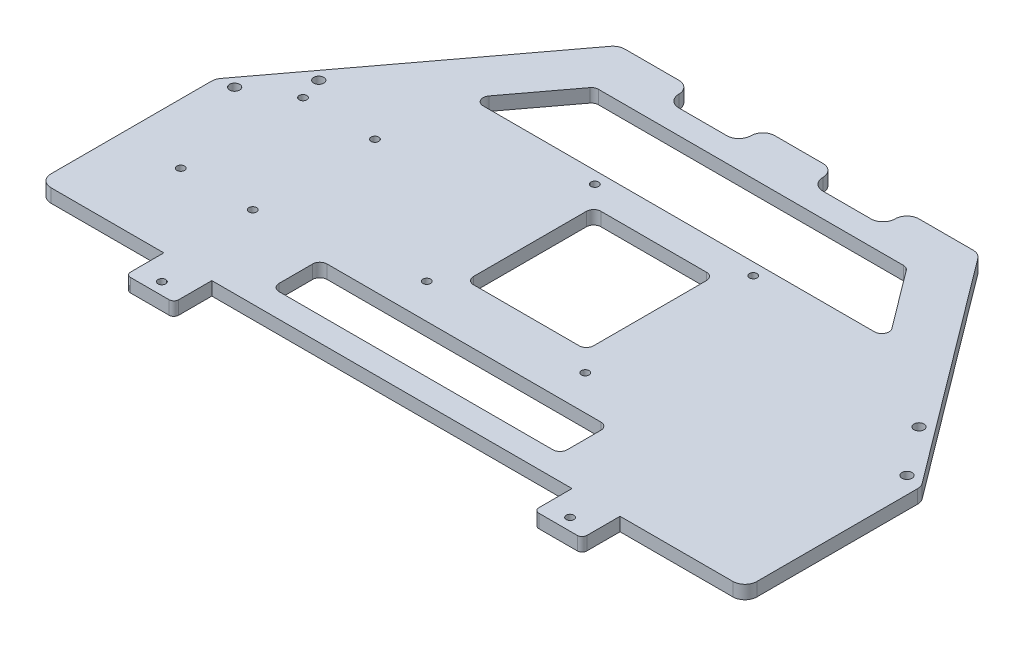
SolidWorks part; units mm, degrees
material "t5ハニカムプラダン"
ref_plane "正面" through (0, 0, 0) normal (0, 0, 1) x (1, 0, 0)
ref_plane "平面" through (0, 0, 0) normal (0, 1, 0) x (1, 0, 0)
ref_plane "右側面" through (0, 0, 0) normal (1, 0, 0) x (0, 0, -1)
sketch "ｽｹｯﾁ1" plane through (0, 0, 0) normal (0, 1, 0) x (1, 0, 0)
  line L0 (0, 0) -> (0, 132.75) construction
  line L1 (-147, 36.75) -> (147, 36.75)
  line L2 (-147, 36.75) -> (-147, -36.75)
  line L3 (-147, -36.75) -> (147, -36.75)
  line L4 (147, 36.75) -> (147, -36.75)
  line L5 (-147, 36.75) -> (147, -36.75) construction
  line L6 (-147, -36.75) -> (147, 36.75) construction
  line L7 (75, 132.75) -> (-75, 132.75)
  line L8 (-75, 132.75) -> (-147, 36.75)
  line L9 (75, 132.75) -> (147, 36.75)
  line L10 (140, 37.75) -> (125, 57.75) construction
  circle A0 centre (140, 37.75) radius 2.1
  circle A1 centre (-140, 37.75) radius 2.1
  circle A2 centre (125, 57.75) radius 2.1
  circle A3 centre (-125, 57.75) radius 2.1
  point P0 (0, 0)
  dimension "D5" = 4.2
  dimension "D1" = 294
  dimension "D2" = 73.5
  dimension "D3" = 169.5
  dimension "D4" = 150
  dimension "D6" = 280
  dimension "D7" = 74.5
  dimension "D8" = 25
extrude "ﾎﾞｽ - 押し出し1" add sketch "ｽｹｯﾁ1" along normal blind 5.6 contours L9 L7 L8 L1 | L4 L1 L2 L3 A0 A1 region at (0, 0, -79.632) region at (0, 0, 0.0097)
sketch "ｽｹｯﾁ2" plane through (0, 0, 0) normal (0, 1, 0) x (1, 0, 0)
  line L0 (-147, -36.75) -> (147, -36.75) construction
  line L1 (-95, -36.75) -> (-75, -36.75)
  line L2 (-95, -36.75) -> (-95, -52.55)
  line L3 (-95, -52.55) -> (-75, -52.55)
  line L4 (-75, -36.75) -> (-75, -52.55)
  line L5 (0, -36.75) -> (0, 132.75) construction
  line L6 (75, 132.75) -> (-75, 132.75) construction
  line L7 (-85, -52.55) -> (-85, -47.55) construction
  line L8 (85, -52.55) -> (85, -47.55) construction
  line L9 (75, -36.75) -> (75, -52.55)
  line L10 (95, -52.55) -> (75, -52.55)
  line L11 (95, -36.75) -> (95, -52.55)
  line L12 (95, -36.75) -> (75, -36.75)
  circle A0 centre (-85, -47.55) radius 1.6
  circle A1 centre (85, -47.55) radius 1.6
  dimension "D3" = 3.2
  dimension "D1" = 15.8
  dimension "D2" = 20
  dimension "D4" = 5
  dimension "D5" = 150
extrude "ﾎﾞｽ - 押し出し2" add sketch "ｽｹｯﾁ2" along normal blind 5.6
sketch "ｽｹｯﾁ3" plane through (0, 5.6, 0) normal (0, 1, 0) x (1, 0, 0)
  line L0 (75, 132.75) -> (-75, 132.75) construction
  line L1 (-30, 77.75) -> (36, 77.75) construction
  line L2 (-30, 77.75) -> (-30, 7.75) construction
  line L3 (-30, 7.75) -> (36, 7.75) construction
  line L4 (36, 77.75) -> (36, 7.75) construction
  line L5 (-30, 77.75) -> (36, 7.75) construction
  line L6 (-30, 7.75) -> (36, 77.75) construction
  line L7 (-147, 36.75) -> (-147, -36.75) construction
  line L8 (3, 77.75) -> (3, 42.75) construction
  line L9 (3, 42.75) -> (36, 42.75) construction
  line L10 (147, 36.75) -> (147, -36.75) construction
  line L11 (22.75, 66.5) -> (51.25, 66.5) construction
  line L12 (22.75, 66.5) -> (22.75, 19) construction
  line L13 (22.75, 19) -> (51.25, 19) construction
  line L14 (51.25, 66.5) -> (51.25, 19) construction
  line L15 (22.75, 66.5) -> (51.25, 19) construction
  line L16 (22.75, 19) -> (51.25, 66.5) construction
  line L17 (37, 66.5) -> (37, 42.75) construction
  line L18 (37, 42.75) -> (51.25, 42.75) construction
  line L19 (22.75, 19) -> (51.25, 19) construction
  line L20 (-107, 48.19) -> (-107, 22.75) construction
  line L21 (-121.995, 48.19) -> (-92.005, 48.19) construction
  line L22 (-121.995, 48.19) -> (-121.995, -2.69) construction
  line L23 (-121.995, -2.69) -> (-92.005, -2.69) construction
  line L24 (-92.005, 48.19) -> (-92.005, -2.69) construction
  line L25 (-121.995, 48.19) -> (-92.005, -2.69) construction
  line L26 (-121.995, -2.69) -> (-92.005, 48.19) construction
  line L27 (-107, 22.75) -> (-92.005, 22.75) construction
  circle A0 centre (36, 77.75) radius 1.6
  circle A1 centre (-30, 77.75) radius 1.6
  circle A2 centre (-30, 7.75) radius 1.6
  circle A3 centre (36, 7.75) radius 1.6
  circle A4 centre (51.25, 66.5) radius 2.1 construction
  circle A5 centre (37, 66.5) radius 2.1 construction
  circle A6 centre (22.75, 66.5) radius 2.1 construction
  circle A7 centre (22.75, 19) radius 2.1 construction
  circle A8 centre (37, 19) radius 2.1 construction
  circle A9 centre (51.25, 19) radius 2.1 construction
  circle A10 centre (-92.005, 48.19) radius 1.6
  circle A11 centre (-92.005, -2.69) radius 1.6
  circle A12 centre (-121.995, -2.69) radius 1.6
  circle A13 centre (-121.995, 48.19) radius 1.6
  point P0 (3, 42.75)
  point P16 (37, 42.75)
  point P33 (-107, 22.75)
  dimension "D5" = 3.2
  dimension "D10" = 4.2
  dimension "D1" = 66
  dimension "D2" = 70
  dimension "D3" = 90
  dimension "D4" = 150
  dimension "D6" = 28.5
  dimension "D7" = 47.5
  dimension "D8" = 90
  dimension "D9" = 110
  dimension "D11" = 29.99
  dimension "D12" = 50.88
  dimension "D13" = 110
  dimension "D14" = 40
extrude "ｶｯﾄ - 押し出し1" cut sketch "ｽｹｯﾁ3" against normal through all
sketch "ｽｹｯﾁ4" plane through (0, 5.6, 0) normal (0, 1, 0) x (1, 0, 0)
  line L0 (36, 7.75) -> (-30, 77.75) construction
  line L1 (131, 24.75) -> (65, 112.75)
  line L2 (-22, 69.2652) -> (28, 69.2652)
  line L3 (-22, 69.2652) -> (-22, 16.2348)
  line L4 (-22, 16.2348) -> (28, 16.2348)
  line L5 (28, 69.2652) -> (28, 61.5)
  line L6 (-22, 69.2652) -> (28, 16.2348) construction
  line L7 (-22, 16.2348) -> (28, 69.2652) construction
  line L8 (65, 112.75) -> (-65, 112.75)
  line L9 (-65, 112.75) -> (-131, 24.75)
  line L10 (-87.5, 82.75) -> (87.5, 82.75)
  line L11 (0, 0) -> (0, -16.75) construction
  line L12 (28, 61.5) -> (28, 24)
  line L13 (-60, -26.75) -> (60, -26.75)
  line L14 (-60, -26.75) -> (-60, -6.75)
  line L15 (-60, -6.75) -> (60, -6.75)
  line L16 (60, -26.75) -> (60, -6.75)
  line L17 (-60, -26.75) -> (60, -6.75) construction
  line L18 (-60, -6.75) -> (60, -26.75) construction
  line L20 (28, 61.5) -> (28, 24) construction
  line L21 (-75, 132.75) -> (-147, 36.75)
  line L22 (-147, 36.75) -> (-147, -36.75)
  line L23 (-147, -36.75) -> (-95, -36.75)
  line L24 (-95, -36.75) -> (-95, -52.55)
  line L25 (-95, -52.55) -> (-75, -52.55)
  line L26 (-75, -52.55) -> (-75, -36.75)
  line L27 (-75, -36.75) -> (75, -36.75)
  line L28 (75, -36.75) -> (75, -52.55)
  line L29 (75, -52.55) -> (95, -52.55)
  line L30 (95, -52.55) -> (95, -36.75)
  line L31 (95, -36.75) -> (147, -36.75)
  line L32 (147, -36.75) -> (147, 36.75)
  line L33 (147, 36.75) -> (75, 132.75)
  line L34 (75, 132.75) -> (-75, 132.75)
  line L35 (-75, 132.75) -> (-147, 36.75)
  line L36 (-147, 36.75) -> (-147, -36.75)
  line L37 (-147, -36.75) -> (-95, -36.75)
  line L38 (-95, -36.75) -> (-95, -52.55)
  line L39 (-95, -52.55) -> (-75, -52.55)
  line L40 (-75, -52.55) -> (-75, -36.75)
  line L41 (-75, -36.75) -> (75, -36.75)
  line L42 (75, -36.75) -> (75, -52.55)
  line L43 (75, -52.55) -> (95, -52.55)
  line L44 (95, -52.55) -> (95, -36.75)
  line L45 (95, -36.75) -> (147, -36.75)
  line L46 (147, -36.75) -> (147, 36.75)
  line L47 (147, 36.75) -> (75, 132.75)
  line L48 (75, 132.75) -> (-75, 132.75)
  line L53 (28, 24) -> (28, 16.2348)
  circle A1 centre (85, -47.55) radius 1.6
  circle A2 centre (85, -47.55) radius 1.6
  circle A3 centre (36, 77.75) radius 1.6
  circle A4 centre (36, 77.75) radius 1.6
  circle A5 centre (-140, 37.75) radius 2.1
  circle A6 centre (-140, 37.75) radius 2.1
  circle A7 centre (140, 37.75) radius 2.1
  circle A8 centre (140, 37.75) radius 2.1
  circle A11 centre (36, 7.75) radius 1.6
  circle A12 centre (36, 7.75) radius 1.6
  circle A13 centre (-30, 7.75) radius 1.6
  circle A14 centre (-30, 7.75) radius 1.6
  circle A15 centre (-30, 77.75) radius 1.6
  circle A16 centre (-30, 77.75) radius 1.6
  circle A17 centre (-121.995, 48.19) radius 1.6
  circle A18 centre (-121.995, 48.19) radius 1.6
  circle A19 centre (-121.995, -2.69) radius 1.6
  circle A20 centre (-121.995, -2.69) radius 1.6
  circle A21 centre (-92.005, -2.69) radius 1.6
  circle A22 centre (-92.005, -2.69) radius 1.6
  circle A23 centre (-92.005, 48.19) radius 1.6
  circle A24 centre (-92.005, 48.19) radius 1.6
  circle A35 centre (-85, -47.55) radius 1.6
  circle A36 centre (-85, -47.55) radius 1.6
  point P0 (3, 42.75)
  point P85 (39.625, 42.75)
  dimension "D19" = 50
  dimension "D22" = 30
  dimension "D23" = 10
  dimension "D24" = 20
  dimension "D25" = 120
  dimension "D1" = 0
  dimension "D2" = 0
  dimension "D3" = 0
  dimension "D4" = 0
  dimension "D6" = 0
  dimension "D7" = 0
  dimension "D8" = 0
  dimension "D9" = 0
  dimension "D10" = 0
  dimension "D11" = 0
  dimension "D12" = 0
  dimension "D18" = 0
  dimension "D20" = 0
  dimension "D21" = 20
extrude "ｶｯﾄ - 押し出し2" cut sketch "ｽｹｯﾁ4" against normal through all contours L9 L10 L1 L8 | L5 L2 L3 L4 | L13 L16 L15 L14 region at (0, 5.6, -97.0123) region at (3, 5.6, -42.75) region at (0, 5.6, 16.75)
sketch "ｽｹｯﾁ6" plane through (0, 5.6, 0) normal (0, 1, 0) x (1, 0, 0)
  line L0 (0, 132.75) -> (0, 127.75) construction
  line L1 (75, 132.75) -> (-75, 132.75) construction
  line L3 (-45, 122.75) -> (45, 122.75)
  line L4 (-45, 122.75) -> (-45, 132.75)
  line L5 (-45, 132.75) -> (45, 132.75)
  line L6 (45, 122.75) -> (45, 132.75)
  line L7 (-45, 122.75) -> (45, 132.75) construction
  line L8 (-45, 132.75) -> (45, 122.75) construction
  dimension "D1" = 90
  dimension "D2" = 10
extrude "ｶｯﾄ - 押し出し3" cut sketch "ｽｹｯﾁ6" against normal through all
sketch "ｽｹｯﾁ7" plane through (0, 5.6, 0) normal (0, 1, 0) x (1, 0, 0)
  line L0 (0, 122.75) -> (0, 127.75) construction
  line L1 (-45, 122.75) -> (45, 122.75) construction
  line L2 (75, 132.75) -> (45, 132.75) construction
  line L3 (-15, 132.75) -> (15, 132.75)
  line L4 (-15, 132.75) -> (-15, 122.75)
  line L5 (-15, 122.75) -> (15, 122.75)
  line L6 (15, 132.75) -> (15, 122.75)
  line L7 (-15, 132.75) -> (15, 122.75) construction
  line L8 (-15, 122.75) -> (15, 132.75) construction
  line L9 (45, 122.75) -> (45, 132.75) construction
  dimension "D1" = 30
extrude "ﾎﾞｽ - 押し出し3" add sketch "ｽｹｯﾁ7" against normal blind 5.6
fillet "ﾌｨﾚｯﾄ1" radius 3 12 edges at (-22, 2.8, -16.2348) (28, 2.8, -16.2348) (87.5, 2.8, -82.75) (28, 2.8, -69.2652) (65, 2.8, -112.75) (-22, 2.8, -69.2652) (-65, 2.8, -112.75) (-87.5, 2.8, -82.75) (60, 2.8, 26.75) (60, 2.8, 6.75) (-60, 2.8, 6.75) (-60, 2.8, 26.75)
fillet "ﾌｨﾚｯﾄ2" radius 5 14 edges at (-147, 2.8, 36.75) (-147, 2.8, -36.75) (-75, 2.8, -132.75) (75, 2.8, -132.75) (147, 2.8, -36.75) (147, 2.8, 36.75) (45, 2.8, -132.75) (45, 2.8, -122.75) (-45, 2.8, -132.75) (-45, 2.8, -122.75) (15, 2.8, -132.75) (15, 2.8, -122.75) (-15, 2.8, -132.75) (-15, 2.8, -122.75)
fillet "ﾌｨﾚｯﾄ3" radius 2 4 edges at (95, 2.8, 52.55) (75, 2.8, 52.55) (-95, 2.8, 52.55) (-75, 2.8, 52.55)
